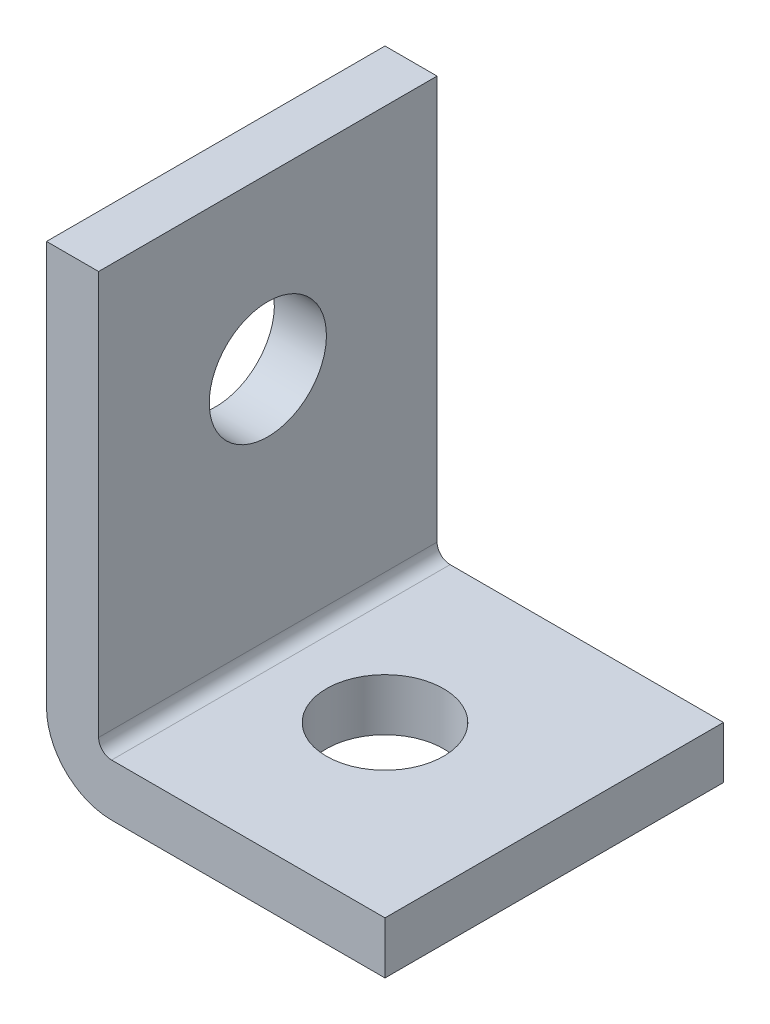
SolidWorks part; units mm, degrees
ref_plane "Front Plane" through (0, 0, 0) normal (0, 0, 1) x (1, 0, 0)
ref_plane "Top Plane" through (0, 0, 0) normal (0, 1, 0) x (1, 0, 0)
ref_plane "Right Plane" through (0, 0, 0) normal (1, 0, 0) x (0, 0, -1)
sketch "Sketch1" plane through (0, 0, 0) normal (0, 0, 1) x (1, 0, 0)
  line L0 (0, 57.15) -> (0, 7.9375)
  line L1 (7.9375, 0) -> (41.275, 0)
  arc A0 (0, 7.9375) -> (7.9375, 0) centre (7.9375, 7.9375) ccw
  dimension "D1" = 7.9375
  dimension "B" = 41.275
  dimension "A" = 57.15
extrude "Extrude-Thin1" add sketch "Sketch1" along normal mid plane 41.275 thin thin type one direction reverse wall 6.35
sketch "Sketch2" plane through (0, 6.35, 0) normal (0, 1, 0) x (1, 0, 0)
  line L0 (41.275, -20.6375) -> (41.275, 20.6375) construction
  circle A0 centre (20.6375, 0) radius 7.1438
  dimension "D1" = 20.6375
  dimension "Hole Size" = 14.2875
extrude "Cut-Extrude1" cut sketch "Sketch2" against normal through all
sketch "Sketch3" plane through (6.35, 0, 0) normal (1, 0, 0) x (0, 0, -1)
  line L0 (-20.6375, 57.15) -> (20.6375, 57.15) construction
  circle A0 centre (0, 36.5125) radius 7.1438
  dimension "D1" = 20.6375
  dimension "D2" = 14.2875
extrude "Cut-Extrude2" cut sketch "Sketch3" against normal through all
